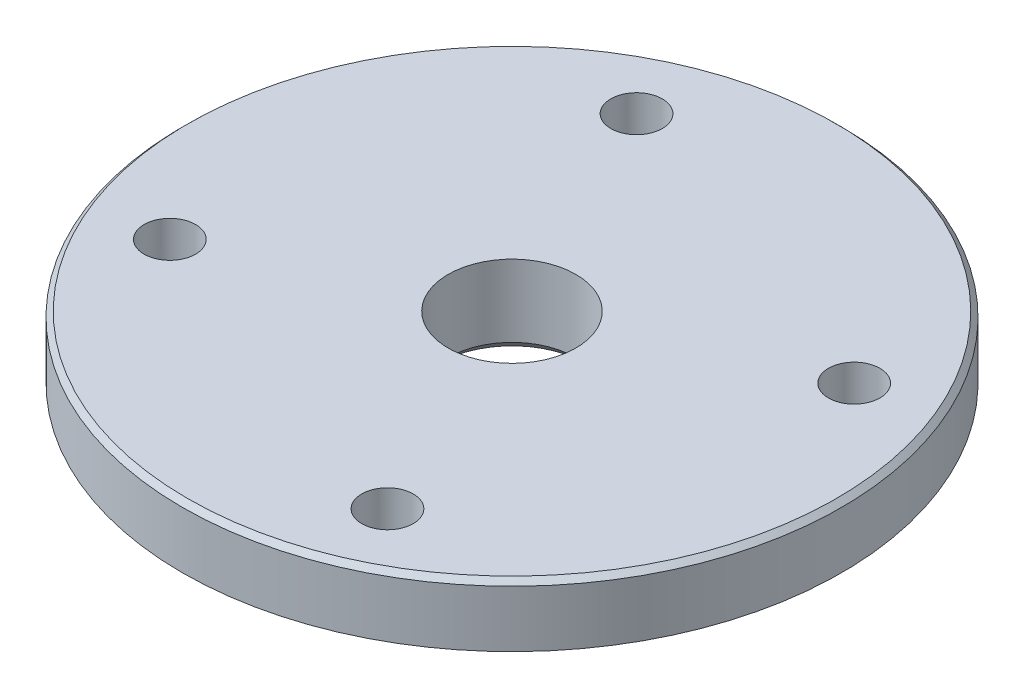
SolidWorks part; units mm, degrees
material "AISI 316 Barra de aço inoxidável recozido (SS)"
ref_plane "Plano frontal" through (0, 0, 0) normal (0, 0, 1) x (1, 0, 0)
ref_plane "Plano superior" through (0, 0, 0) normal (0, 1, 0) x (1, 0, 0)
ref_plane "Plano direito" through (0, 0, 0) normal (1, 0, 0) x (0, 0, -1)
sketch "Esboço1" plane through (0, 0, 0) normal (0, 0, 1) x (1, 0, 0)
  line L0 (0, 0) -> (0, 22.7862) construction
  line L1 (0, 0) -> (16, 0) construction
  line L2 (3.1, 1.5) -> (3.1, -2.5)
  line L5 (3.1, -2.5) -> (9, -2.5)
  line L6 (16, 1.5) -> (16, -1.5)
  line L7 (9, -2.5) -> (9, -1.5)
  line L8 (9, -1.5) -> (16, -1.5)
  line L9 (16, 1.5) -> (3.1, 1.5)
  dimension "D1" = 16
  dimension "D2" = 3.1
  dimension "D3" = 3
  dimension "D4" = 5.9
  dimension "D5" = 1
revolve "Revolução1" add sketch "Esboço1" angle 360 about L0
ref_plane "Plano2" through (0, 1.5, 0) normal (0, 1, 0) x (1, 0, 0)
ref_axis "Eixo1" through (0, 16.485, 0) along (0, -1, 0)
ref_axis "Eixo2" through (0, -3.2393, 0) along (0, 1, 0)
chamfer "Chanfro1" distance 0.5 angle 45 1 edges at (0, -2.5, -3.1)
ref_axis "Eixo3" through (0, -2.7, 0) along (0, 1, 0)
hole_wizard "Furo roscado de M3x0.52" positions "Esboço5" profile "Esboço4" tap size "M3x0.5" standard "Ansi Metric" end condition up to next
sketch "Esboço5" plane through (0, 1.5, 0) normal (0, 1, 0) x (1, 0, 0)
  line L0 (0, 0) -> (0, 16) construction
  line L2 (0, 0) -> (14.5009, 6.7619) construction
  circle A0 centre (0, 0) radius 12.5
  circle A1 centre (0, 0) radius 16 construction
  point P0 (11.3288, 5.2827)
  dimension "D2" = 25
  dimension "D1" = 65
sketch "Esboço4" plane through (11.3288, 1.5, -5.2827) normal (1, 0, 0) x (0, 0, 1)
  line L0 (0, 0) -> (0, 3.001)
  line L1 (0, 3.001) -> (1.25, 3.001)
  line L2 (1.25, 3.001) -> (1.25, 0)
  line L5 (1.25, 0) -> (0, 0)
  line L11 (0, -6.35) -> (0, 107.95) construction
  dimension "Thread Major Dia." = 2.5
  dimension "Thru Tap Drill Depth" = 3.001
pattern_circular "PadrãoCircular2" count 4 every 90 about axis through (0, -2.7, 0) along (0, 1, 0) of "Furo roscado de M3x0.52"
chamfer "Chanfro2" distance 0.2 angle 45 1 edges at (0, -2.5, -9)
chamfer "Chanfro3" distance 0.25 angle 45 1 edges at (0, 1.5, -16)
fillet "Filete3" radius 0.2 1 edges at (0, -1.5, -9)
